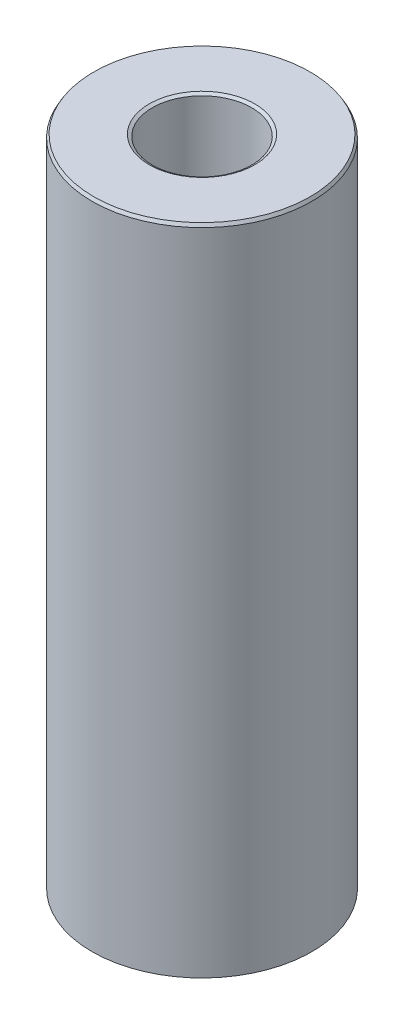
SolidWorks part; units mm, degrees
ref_plane "Front Plane" through (0, 0, 0) normal (0, 0, 1) x (1, 0, 0)
ref_plane "Top Plane" through (0, 0, 0) normal (0, 1, 0) x (1, 0, 0)
ref_plane "Right Plane" through (0, 0, 0) normal (1, 0, 0) x (0, 0, -1)
sketch "Sketch1" plane through (0, 0, 0) normal (0, 1, 0) x (1, 0, 0)
  circle A0 centre (0, 0) radius 12.5
  dimension "SLEEVE_OD" = 25
extrude "Boss-Extrude1" add sketch "Sketch1" along normal blind 74.4313
sketch "Sketch2" plane through (0, 0, 0) normal (0, 1, 0) x (1, 0, 0)
  circle A0 centre (0, 0) radius 5.6516
  dimension "BORE_D" = 11.3032
extrude "Cut-Extrude1" cut sketch "Sketch2" along normal through all
chamfer "Chamfer1" distance 0.3501 angle 30 4 edges at (0, 74.4313, 5.6516) (0, 0, 5.6516) (0, 0, 12.5) (0, 74.4313, 12.5) first distance on face at (0, 74.4313, 5.6516) first distance on face at (0, 0, 5.6516) first distance on face at (0, 74.4313, 12.5)
